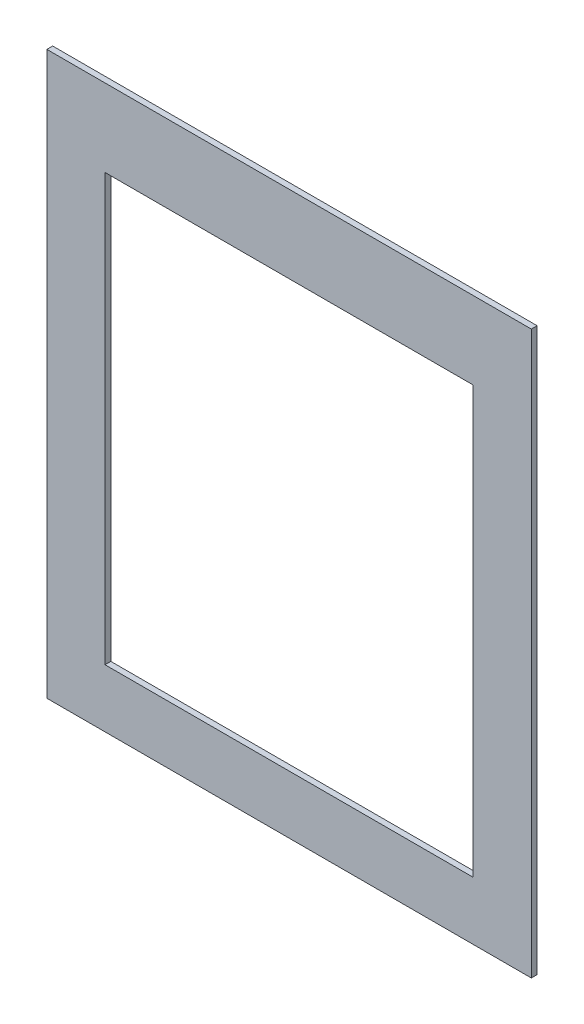
SolidWorks part; units mm, degrees
material "Клен"
ref_plane "Спереди" through (0, 0, 0) normal (0, 0, 1) x (1, 0, 0)
ref_plane "Сверху" through (0, 0, 0) normal (0, 1, 0) x (1, 0, 0)
ref_plane "Справа" through (0, 0, 0) normal (1, 0, 0) x (0, 0, -1)
sketch "Эскиз1" plane through (0, 0, 0) normal (0, 0, 1) x (1, 0, 0)
  line L0 (2.3279, 480.4642) -> (2.3279, 40.4642)
  line L1 (-57.6721, 560.4642) -> (442.3279, 560.4642)
  line L2 (-57.6721, 560.4642) -> (-57.6721, -19.5358)
  line L3 (-57.6721, -19.5358) -> (442.3279, -19.5358)
  line L4 (442.3279, 560.4642) -> (442.3279, -19.5358)
  line L5 (2.3279, 40.4642) -> (382.3279, 40.4642)
  line L6 (382.3279, 480.4642) -> (382.3279, 40.4642)
  line L7 (2.3279, 480.4642) -> (382.3279, 480.4642)
  dimension "D1" = 80
  dimension "D2" = 500
  dimension "D3" = 60
  dimension "D4" = 380
  dimension "D5" = 60
  dimension "D6" = 60
extrude "Бобышка-Вытянуть1" add sketch "Эскиз1" along normal blind 6
equation "\"sheet_thickness\"= 6"
equation "\"D1@Бобышка-Вытянуть1\"= \"sheet_thickness\""
equation "\"bottom_line\"= 60"
equation "\"width_space\"= 500"
equation "\"D6@Эскиз1\"=\"D5@Эскиз1\""
